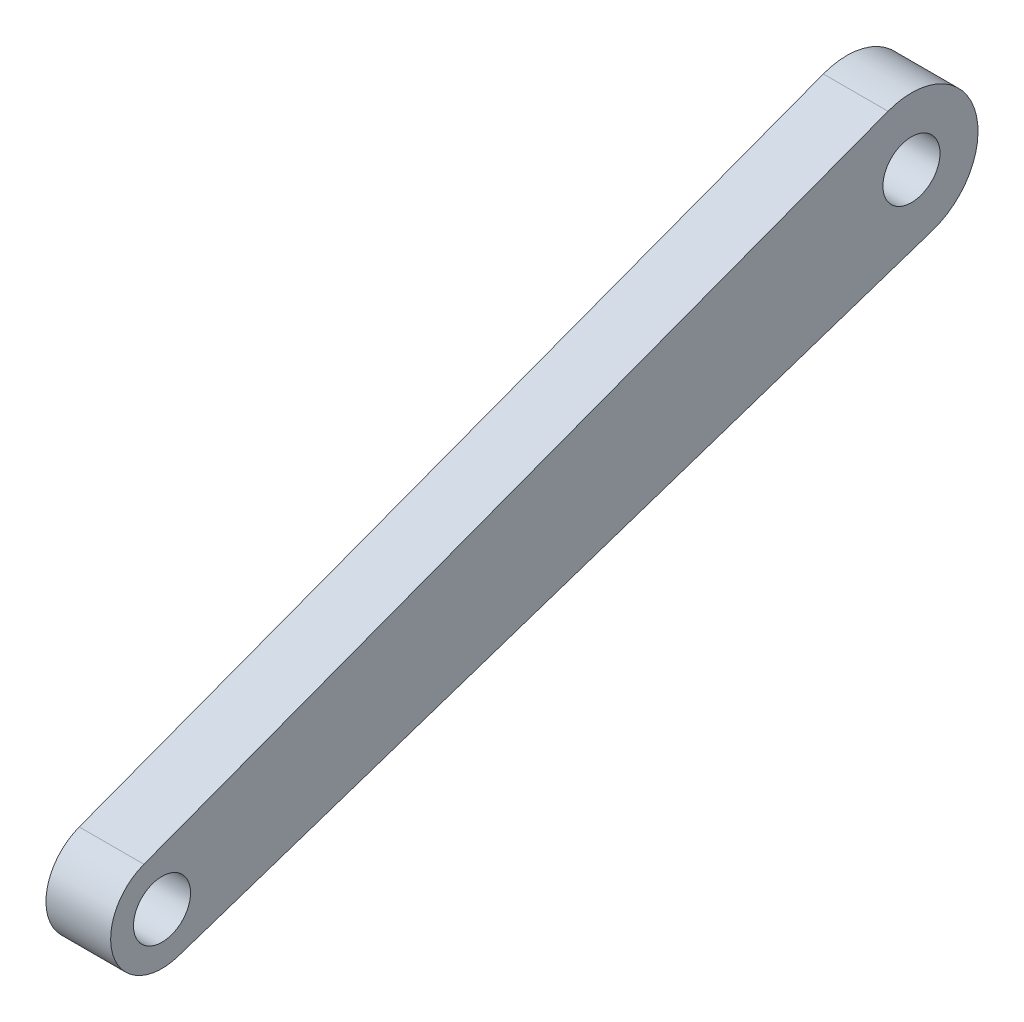
SolidWorks part; units mm, degrees
ref_plane "Front Plane" through (0, 0, 0) normal (0, 0, 1) x (1, 0, 0)
ref_plane "Top Plane" through (0, 0, 0) normal (0, 1, 0) x (1, 0, 0)
ref_plane "Right Plane" through (0, 0, 0) normal (1, 0, 0) x (0, 0, -1)
sketch "Sketch1" plane through (0, 0, 0) normal (1, 0, 0) x (0, 0, -1)
  line L0 (0, 0) -> (54.66, 0) construction
  line L1 (54.66, 0) -> (54.66, -8) construction
  line L2 (0, 0) -> (4.9793, -4.1781) construction
  line L3 (54.66, -8) -> (44.385, 9.7968) construction
  line L4 (0, 0) -> (0, -32.6876) construction
  line L5 (4.0283, -1.6511) -> (43.1522, 13.0725)
  line L6 (45.4915, 6.4763) -> (5.8329, -6.7396)
  circle A2 centre (44.385, 9.7968) radius 1.5
  circle A3 centre (4.9793, -4.1781) radius 1.5
  circle A4 centre (44.385, 9.7968) radius 3.5
  circle A5 centre (4.9793, -4.1781) radius 2.7
  dimension "D7" = 3
  dimension "D8" = 3
  dimension "D9" = 5.4
  dimension "D10" = 7
  dimension "D1" = 54.66
  dimension "D2" = 8
  dimension "D3" = 50
  dimension "D4" = 30
  dimension "D5" = 6.5
  dimension "D6" = 20.55
extrude "Boss-Extrude1" add sketch "Sketch1" along normal blind 1.7 and the other way blind 1.7 contours A5 L6 A4 L5 | A5 A3 | A4 A2 region at (0, 2.9347, -25.0355) region at (0, -2.0208, -6.4724) region at (0, 12.5933, -46.3206)
